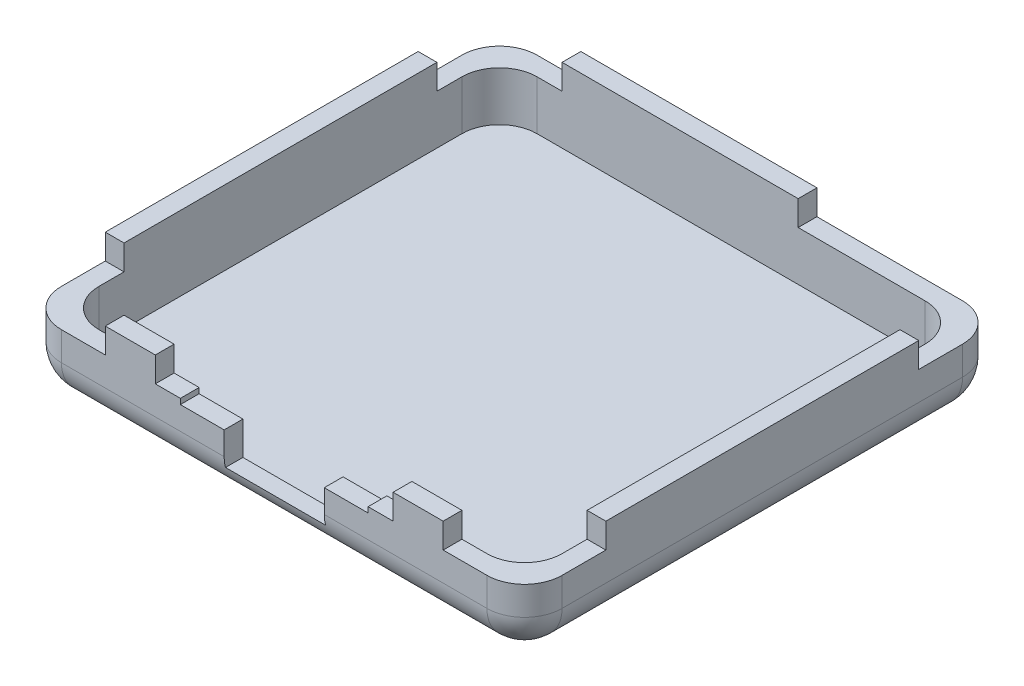
SolidWorks part; units mm, degrees
ref_plane "Front Plane" through (0, 0, 0) normal (0, 0, 1) x (1, 0, 0)
ref_plane "Top Plane" through (0, 0, 0) normal (0, 1, 0) x (1, 0, 0)
ref_plane "Right Plane" through (0, 0, 0) normal (1, 0, 0) x (0, 0, -1)
sketch "Sketch1" plane through (0, 0, 0) normal (0, 1, 0) x (1, 0, 0)
  line L1 (-31.4442, 30.054) -> (2.5558, 30.054)
  line L2 (-34.4442, 27.054) -> (-34.4442, -4.946)
  line L3 (-31.4442, -7.946) -> (2.5558, -7.946)
  line L4 (5.5558, 27.054) -> (5.5558, -4.946)
  arc A0 (-34.4442, -4.946) -> (-31.4442, -7.946) centre (-31.4442, -4.946) ccw
  arc A1 (2.5558, -7.946) -> (5.5558, -4.946) centre (2.5558, -4.946) ccw
  arc A2 (2.5558, 30.054) -> (5.5558, 27.054) centre (2.5558, 27.054) cw
  arc A3 (-31.4442, 30.054) -> (-34.4442, 27.054) centre (-31.4442, 27.054) ccw
  dimension "D1" = 3
  dimension "D2" = 34
  dimension "D3" = 32
extrude "Boss-Extrude1" add sketch "Sketch1" along normal blind 7.2884
sketch "Sketch2" plane through (0, 7.2884, 0) normal (0, 1, 0) x (1, 0, 0)
  line L0 (2.5558, 30.054) -> (-31.4442, 30.054) construction
  line L1 (-29.9442, 28.554) -> (1.0558, 28.554)
  line L2 (-32.9442, 25.554) -> (-32.9442, -3.446)
  line L3 (-29.9442, -6.446) -> (1.0558, -6.446)
  line L4 (4.0558, 25.554) -> (4.0558, -3.446)
  line L5 (5.5558, -4.946) -> (5.5558, 27.054) construction
  line L6 (-31.4442, -7.946) -> (2.5558, -7.946) construction
  line L7 (-34.4442, 27.054) -> (-34.4442, -4.946) construction
  arc A0 (-32.9442, -3.446) -> (-29.9442, -6.446) centre (-29.9442, -3.446) ccw
  arc A1 (1.0558, -6.446) -> (4.0558, -3.446) centre (1.0558, -3.446) ccw
  arc A2 (1.0558, 28.554) -> (4.0558, 25.554) centre (1.0558, 25.554) cw
  arc A3 (-29.9442, 28.554) -> (-32.9442, 25.554) centre (-29.9442, 25.554) ccw
  dimension "D1" = 3
  dimension "D2" = 1.5
  dimension "D3" = 1.5
  dimension "D4" = 1.5
  dimension "D5" = 1.5
extrude "Cut-Extrude3" cut sketch "Sketch2" against normal blind 5.9386
sketch "Sketch5" plane through (0, 0, 7.946) normal (0, 0, 1) x (1, 0, 0)
  line L1 (-18.4442, 4.998) -> (-10.4442, 4.998)
  line L2 (-18.4442, 4.998) -> (-18.4442, 2.198)
  line L3 (-18.4442, 2.198) -> (-10.4442, 2.198)
  line L4 (-10.4442, 4.998) -> (-10.4442, 2.198)
  line L7 (-21.9442, 5.9375) -> (-6.9442, 5.9375)
  line L8 (-21.9442, 5.9375) -> (-21.9442, 4.8545)
  line L9 (-21.9442, 4.8545) -> (-6.9442, 4.8545)
  line L10 (-6.9442, 5.9375) -> (-6.9442, 4.8545)
  line M7 (2.5558, 7.2884) -> (-31.4442, 7.2884)
  dimension "D1" = 2.8
  dimension "D2" = 8
  dimension "D5" = 1.083
  dimension "D6" = 15
extrude "Cut-Extrude6" cut sketch "Sketch5" against normal blind 4 contours L9 L2 L3 L4 | L10 L8 L9 L2 L1 L4 M7 | L1 L4 L3 L2 region at (-14.4442, 5.4317, 7.946) region at (-14.4442, 3.5263, 7.946)
fillet "Fillet2" radius 3 8 edges at (-14.4442, 0, 7.946) (4.6771, 0, 7.0673) (5.5558, 0, -11.054) (4.6771, 0, -29.1753) (-14.4442, 0, -30.054) (-33.5655, 0, -29.1753) (-34.4442, 0, -11.054) (-33.5655, 0, 7.0673)
sketch "Sketch7" plane through (0, 7.2884, 0) normal (0, 1, 0) x (1, 0, 0)
  line L1 (-4.9442, -10.0971) -> (-23.9442, -10.0971)
  line L2 (-4.9442, -10.0971) -> (-4.9442, -4.0637)
  line L3 (-4.9442, -4.0637) -> (-23.9442, -4.0637)
  line L4 (-23.9442, -10.0971) -> (-23.9442, -4.0637)
  dimension "D1" = 19
  dimension "D2" = 6
  dimension "D3" = 6
extrude "Cut-Extrude8" cut sketch "Sketch7" against normal blind 2
sketch "Sketch8" plane through (0, 7.2884, 0) normal (0, 1, 0) x (1, 0, 0)
  line L1 (13.3902, -12.7905) -> (-0.9442, -12.7905)
  line L2 (13.3902, -12.7905) -> (13.3902, -1.446)
  line L3 (13.3902, -1.446) -> (-0.9442, -1.446)
  line L4 (-0.9442, -12.7905) -> (-0.9442, -1.446)
  line L5 (-27.9442, -18.581) -> (-40.2226, -18.581)
  line L6 (-27.9442, -18.581) -> (-27.9442, -1.446)
  line L7 (-27.9442, -1.446) -> (-40.2226, -1.446)
  line L8 (-40.2226, -18.581) -> (-40.2226, -1.446)
  line L9 (-43.202, 23.554) -> (-27.9442, 23.554)
  line L10 (-43.202, 23.554) -> (-43.202, 32.9642)
  line L11 (-43.202, 32.9642) -> (-27.9442, 32.9642)
  line L12 (-27.9442, 23.554) -> (-27.9442, 32.9642)
  line L13 (11.2909, 23.554) -> (-0.9442, 23.554)
  line L14 (11.2909, 23.554) -> (11.2909, 37.2968)
  line L15 (11.2909, 37.2968) -> (-0.9442, 37.2968)
  line L16 (-0.9442, 23.554) -> (-0.9442, 37.2968)
  dimension "D1" = 5
  dimension "D2" = 5
  dimension "D3" = 5
  dimension "D4" = 5
  dimension "D5" = 5
  dimension "D6" = 5
  dimension "D7" = 5
  dimension "D8" = 5
extrude "Cut-Extrude9" cut sketch "Sketch8" against normal blind 2
sketch "Sketch9" plane through (0, 7.2884, 0) normal (0, 1, 0) x (1, 0, 0)
  line L1 (2.9199, 23.1293) -> (-9.0801, 23.1293)
  line L2 (2.9199, 23.1293) -> (2.9199, 33.6744)
  line L3 (2.9199, 33.6744) -> (-9.0801, 33.6744)
  line L4 (-9.0801, 23.1293) -> (-9.0801, 33.6744)
  dimension "D1" = 12
extrude "Cut-Extrude10" cut sketch "Sketch9" against normal blind 2
